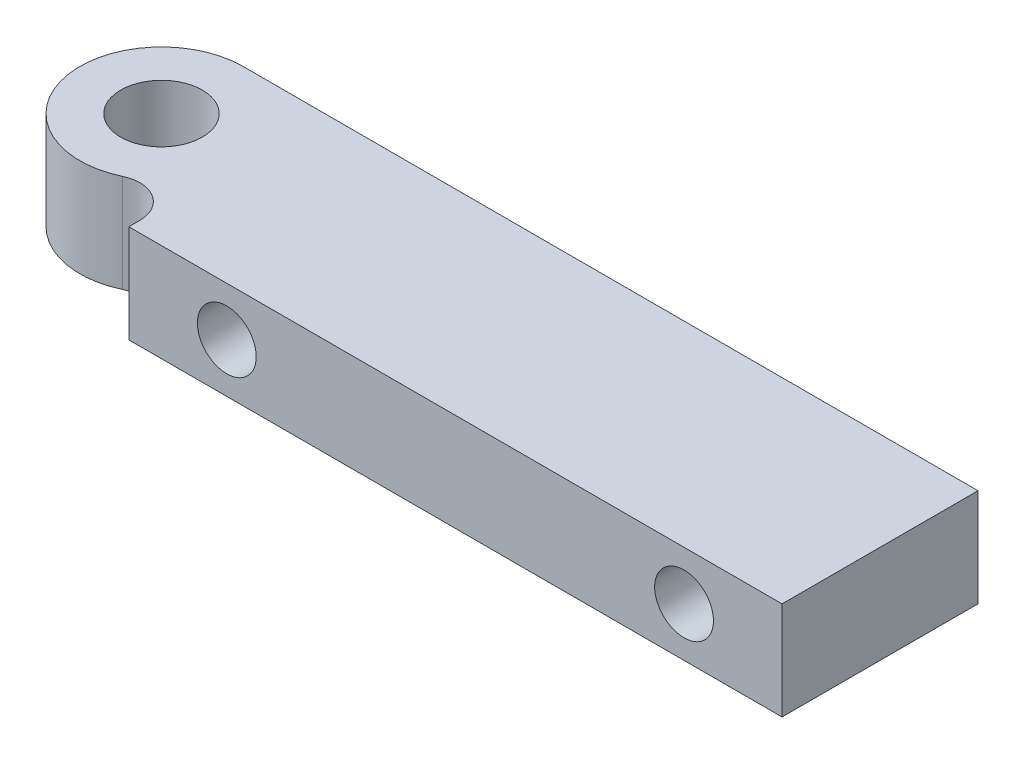
SolidWorks part; units mm, degrees
ref_plane "Front Plane" through (0, 0, 0) normal (0, 0, 1) x (1, 0, 0)
ref_plane "Top Plane" through (0, 0, 0) normal (0, 1, 0) x (1, 0, 0)
ref_plane "Right Plane" through (0, 0, 0) normal (1, 0, 0) x (0, 0, -1)
sketch "Sketch1" plane through (0, 0, 0) normal (0, 1, 0) x (1, 0, 0)
  line L0 (0, 6.35) -> (12.3665, 6.35)
  line L1 (12.3665, 6.35) -> (57.15, 6.35)
  line L2 (6.35, 0) -> (6.35, -8.89)
  line L3 (6.35, -8.89) -> (57.15, -8.89)
  line L4 (57.15, 6.35) -> (57.15, -8.89)
  circle A0 centre (0, 0) radius 3.175
  arc A1 (0, 6.35) -> (6.35, 0) centre (0, 0) ccw
  dimension "D1" = 12.7
  dimension "D2" = 6.35
  dimension "D3" = 6.35
  dimension "D4" = 50.8
  dimension "D5" = 15.24
extrude "Boss-Extrude1" add sketch "Sketch1" along normal mid plane 7.62
fillet "Fillet1" radius 2.54 1 edges at (6.35, 0, 0)
sketch "Sketch2" plane through (0, 0, 8.89) normal (0, 0, 1) x (1, 0, 0)
  circle A0 centre (49.53, 0) radius 1.8987 construction
  circle A1 centre (13.97, 0) radius 1.8987 construction
  circle A2 centre (49.53, 0) radius 1.8986
  circle A3 centre (13.97, 0) radius 1.8987
  circle A4 centre (13.97, 0) radius 2.286
  circle A5 centre (49.53, 0) radius 2.286
  dimension "D1" = 4.572
  dimension "D2" = 4.572
extrude "Cut-Extrude1" cut sketch "Sketch2" against normal blind 5.08 contours A4 | A5 | A3 | A2 region at (49.53, 0, 8.89) region at (13.97, 0, 8.89) region at (11.7487, 0, 8.89) region at (47.3087, 0, 8.89)
